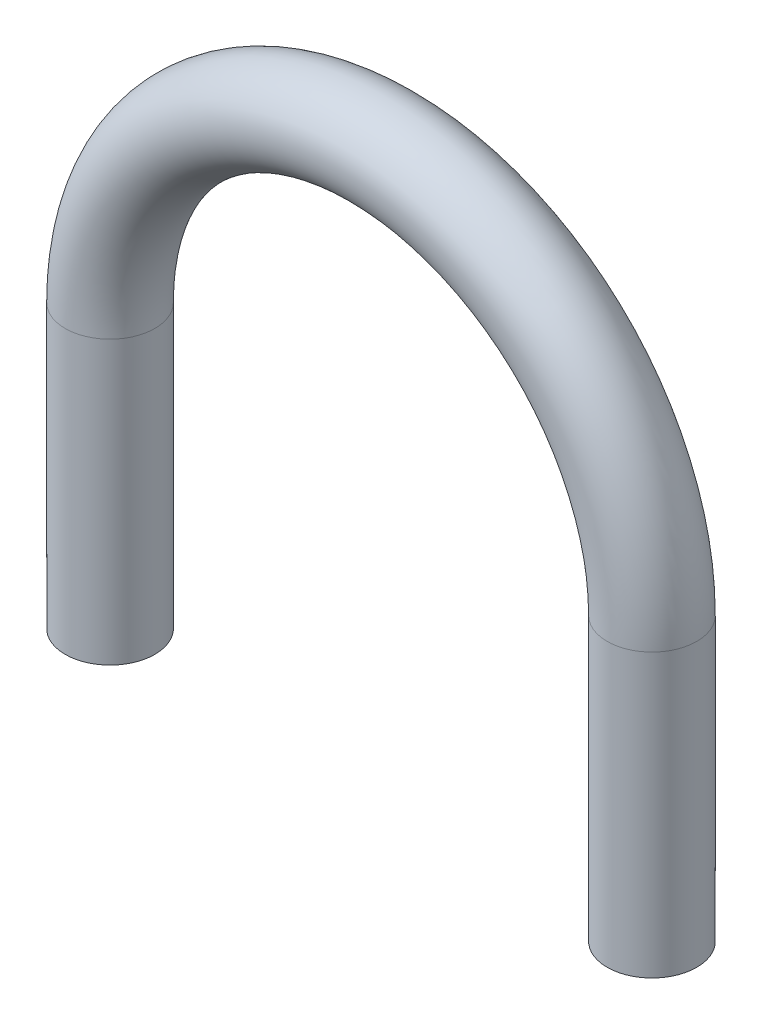
SolidWorks part; units mm, degrees
ref_plane "Plan de face" through (0, 0, 0) normal (0, 0, 1) x (1, 0, 0)
ref_plane "Plan de dessus" through (0, 0, 0) normal (0, 1, 0) x (1, 0, 0)
ref_plane "Plan de droite" through (0, 0, 0) normal (1, 0, 0) x (0, 0, -1)
sketch "Esquisse1" plane through (0, 0, 0) normal (0, 0, 1) x (1, 0, 0)
  line L0 (-19.2, -20) -> (-19.2, 0)
  line L1 (19.2, -20) -> (19.2, 0)
  arc A0 (-19.2, 0) -> (19.2, 0) centre (0, 0) cw
sweep "Balayage3" add path "Esquisse1" circular profile diameter 6.35 parameters "D3"=6.35
